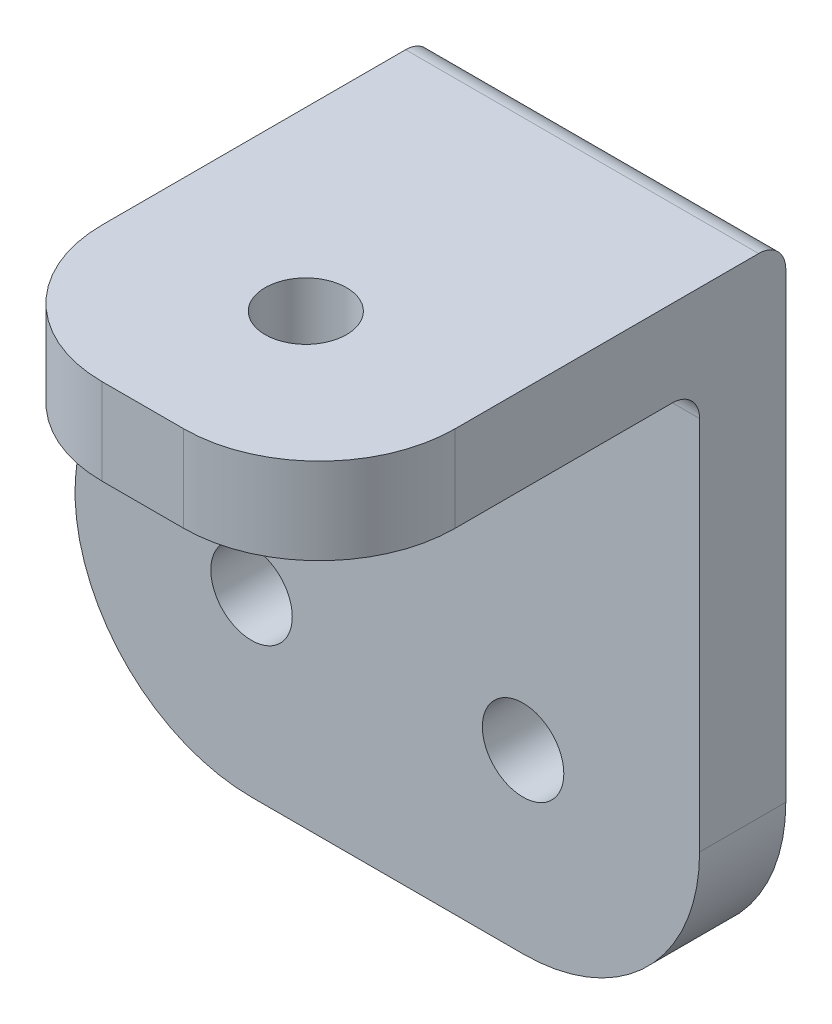
SolidWorks part; units mm, degrees
ref_plane "Front Plane" through (0, 0, 0) normal (0, 0, 1) x (1, 0, 0)
ref_plane "Top Plane" through (0, 0, 0) normal (0, 1, 0) x (1, 0, 0)
ref_plane "Right Plane" through (0, 0, 0) normal (1, 0, 0) x (0, 0, -1)
sketch "Sketch1" plane through (0, 0, 0) normal (0, 0, 1) x (1, 0, 0)
  line L0 (-6.5, 0) -> (-6.5, 18)
  line L1 (-6.5, 18) -> (6.5, 18)
  line L2 (6.5, 18) -> (6.5, 0)
  circle A0 centre (0, 0) radius 1.5
  circle A1 centre (0, 0) radius 6.5
  dimension "D1" = 3
  dimension "D3" = 18
  dimension "D2" = 5
extrude "Boss-Extrude1" add sketch "Sketch1" along normal blind 3.175 contours A1 A0 | A1 L2 L1 L0 region at (0, 11.4709, 0) region at (0, 6.3162, 0)
sketch "Sketch2" plane through (0, 0, 3.175) normal (0, 0, 1) x (1, 0, 0)
  line L0 (6.5, 18) -> (6.5, 0) construction
  line L1 (-6.5, 18) -> (6.5, 18)
  line L2 (-6.5, 18) -> (-6.5, 14.825)
  line L3 (-6.5, 14.825) -> (6.5, 14.825)
  line L4 (6.5, 18) -> (6.5, 14.825)
  dimension "D1" = 3.175
extrude "Boss-Extrude2" add sketch "Sketch2" along normal blind 14
sketch "Sketch3" plane through (0, 18, 0) normal (0, 1, 0) x (1, 0, 0)
  line L0 (6.5, -17.175) -> (-6.5, -17.175) construction
  circle A0 centre (0, -11.175) radius 1.5
  dimension "D1" = 3
  dimension "D2" = 6
extrude "Cut-Extrude1" cut sketch "Sketch3" against normal blind 18
fillet "Fillet1" radius 5 2 edges at (-6.5, 16.4125, 17.175) (6.5, 16.4125, 17.175)
sketch "Sketch4" plane through (0, 0, 0) normal (0, 0, -1) x (-1, 0, 0)
  line L0 (0, -6.5) -> (10, -6.5)
  line L1 (10, 6.5) -> (6.5, 6.5)
  line L2 (6.5, 0) -> (6.5, 18) construction
  circle A0 centre (10, 0) radius 1.5
  circle A1 centre (10, 0) radius 6.5
  arc A2 (-6.5, 0) -> (6.5, 0) centre (0, 0) ccw construction
  line M2 (6.5, 0) -> (6.5, 18)
  arc M5 (-6.5, 0) -> (6.5, 0) centre (0, 0) ccw
  dimension "D1" = 3
  dimension "D3" = 10
  dimension "D2" = 5
extrude "Boss-Extrude3" add sketch "Sketch4" against normal up to surface (3.175 mm away) contours A1 L0 M2 M5 | A1 A0 region at (-5, -5.8248, 0) region at (-7.3121, -5.727, 0) up to face at (0, 5.7875, 3.175)
fillet "Fillet3" radius 1 2 edges at (0, 18, 0) (0, 14.825, 3.175)
chamfer "Chamfer1" distance 5 angle 45 1 edges at (-6.5, 5.4772, 1.5875) first distance on face at (-6.5, 13.4805, 4.4326)
